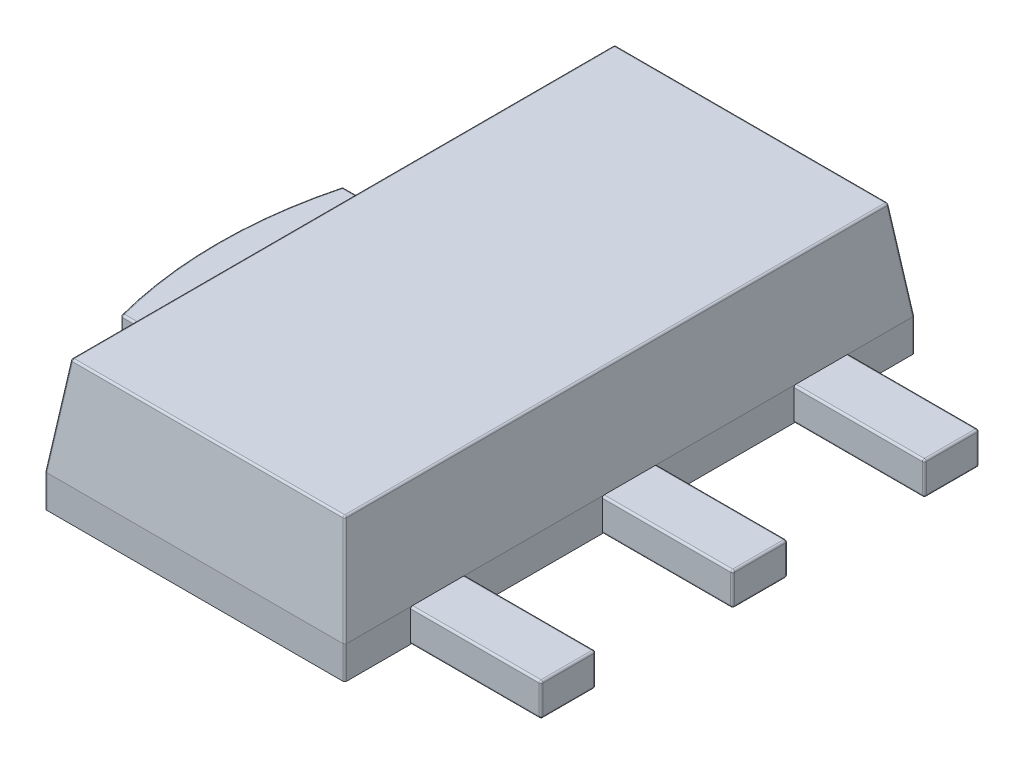
SolidWorks part; units mm, degrees
ref_plane "Front Plane" through (0, 0, 0) normal (0, 0, 1) x (1, 0, 0)
ref_plane "Top Plane" through (0, 0, 0) normal (0, 1, 0) x (1, 0, 0)
ref_plane "Right Plane" through (0, 0, 0) normal (1, 0, 0) x (0, 0, -1)
sketch "Sketch1" plane through (0, 0, 0) normal (0, 1, 0) x (1, 0, 0)
  line L1 (-1.15, -2.185) -> (1.15, -2.185)
  line L2 (-1.15, -2.185) -> (-1.15, 2.185)
  line L3 (-1.15, 2.185) -> (1.15, 2.185)
  line L4 (1.15, -2.185) -> (1.15, 2.185)
  line L5 (-1.15, -2.185) -> (1.15, 2.185) construction
  line L6 (-1.15, 2.185) -> (1.15, -2.185) construction
  point P0 (0, 0)
  dimension "D1" = 2.3
  dimension "D2" = 4.37
extrude "Boss-Extrude1" add sketch "Sketch1" along normal mid plane 1
sketch "Sketch2" plane through (0, 0, 2.185) normal (0, 0, 1) x (1, 0, 0)
  line L0 (-1.15, -0.25) -> (1.15, -0.25) construction
  line L1 (-1.15, 0.5) -> (-1.15, -0.5) construction
  line L2 (1.15, 0.5) -> (1.15, -0.5) construction
  line L3 (-1.15, -0.5) -> (1.15, -0.5) construction
  line L4 (-1.15, -0.25) -> (-1.15, 0.5)
  line L5 (-1.15, 0.5) -> (-1.05, 0.5)
  line L6 (-1.15, 0.5) -> (1.15, 0.5) construction
  line L7 (-1.05, 0.5) -> (-1.15, -0.25)
  line L8 (0, -0.25) -> (0, 0.5) construction
  line L9 (1.05, 0.5) -> (1.15, -0.25)
  line L10 (1.15, 0.5) -> (1.05, 0.5)
  line L11 (1.15, -0.25) -> (1.15, 0.5)
  dimension "D1" = 0.25
  dimension "D2" = 0.1
extrude "Cut-Extrude1" cut sketch "Sketch2" against normal through all
sketch "Sketch3" plane through (1.15, 0, 0) normal (1, 0, 0) x (0, 0, -1)
  line L0 (-2.185, -0.25) -> (-2.185, 0.5)
  line L1 (-2.185, 0.5) -> (-2.085, 0.5)
  line L2 (2.185, 0.5) -> (-2.185, 0.5) construction
  line L3 (-2.085, 0.5) -> (-2.185, -0.25)
  line L4 (0, 0) -> (0, 1.1486) construction
  line L5 (2.085, 0.5) -> (2.185, -0.25)
  line L6 (2.185, 0.5) -> (2.085, 0.5)
  line L7 (2.185, -0.25) -> (2.185, 0.5)
  dimension "D1" = 0.1
extrude "Cut-Extrude2" cut sketch "Sketch3" against normal through all
fillet "Fillet1" radius 0.015 12 edges at (0, 0.5, -2.085) (1.05, 0.5, 0) (0, 0.5, 2.085) (-1.05, 0.5, 0) (-1.15, -0.375, 2.185) (-1.1, 0.125, 2.135) (-1.15, -0.375, -2.185) (-1.1, 0.125, -2.135) (1.15, -0.375, -2.185) (1.1, 0.125, -2.135) (1.1, 0.125, 2.135) (1.15, -0.375, 2.185)
sketch "Sketch6" plane through (0, -0.5, 0) normal (0, -1, 0) x (1, 0, 0)
  line L0 (-1.15, -2.17) -> (-1.15, 2.17) construction
  line L5 (-1.15, 0.85) -> (-1.9, -0.85) construction
  line L6 (-1.15, -0.85) -> (-1.9, 0.85) construction
  line L7 (1.15, -2.17) -> (1.15, 2.17) construction
  line L12 (1.15, 0.21) -> (2.15, -0.21) construction
  line L13 (1.15, -0.21) -> (2.15, 0.21) construction
  line L14 (1.15, 1.68) -> (1.15, 1.26)
  line L15 (1.15, 1.68) -> (2.15, 1.68)
  line L16 (2.15, 1.68) -> (2.15, 1.26)
  line L17 (1.15, 1.26) -> (2.15, 1.26)
  line L18 (1.15, 0.21) -> (1.15, -0.21)
  line L19 (1.15, 0.21) -> (2.15, 0.21)
  line L20 (2.15, 0.21) -> (2.15, -0.21)
  line L21 (1.15, -0.21) -> (2.15, -0.21)
  line L22 (1.15, -1.26) -> (1.15, -1.68)
  line L23 (1.15, -1.26) -> (2.15, -1.26)
  line L24 (2.15, -1.26) -> (2.15, -1.68)
  line L25 (1.15, -1.68) -> (2.15, -1.68)
  line L26 (-1.9, 0.85) -> (-1.15, 0.85)
  line L27 (-1.15, 0.85) -> (-1.15, -0.85)
  line L28 (-1.9, -0.85) -> (-1.15, -0.85)
  arc A0 (-1.9, 0.85) -> (-1.9, -0.85) centre (1.2887, 0) ccw
  point P4 (-1.525, 0)
  point P13 (1.65, 0)
  dimension "D3" = 3.3
  dimension "D1" = 0.75
  dimension "D2" = 1.7
  dimension "D4" = 1
  dimension "D5" = 0.42
extrude "Boss-Extrude2" add sketch "Sketch6" against normal blind 0.25
fillet "Fillet2" radius 0.015 32 edges at (2.15, -0.375, 1.68) (2.15, -0.25, 1.47) (2.15, -0.375, 1.26) (2.15, -0.5, 1.47) (-1.525, -0.5, 0.85) (-1.525, -0.25, 0.85) (-1.9, -0.375, 0.85) (-2.0113, -0.5, 0) (-1.525, -0.5, -0.85) (-1.9, -0.375, -0.85) (-2.0113, -0.25, 0) (-1.525, -0.25, -0.85) (1.65, -0.5, -1.26) (2.15, -0.5, -1.47) (1.65, -0.5, -1.68) (2.15, -0.375, -1.68) (2.15, -0.375, -1.26) (1.65, -0.25, -1.26) (2.15, -0.25, -1.47) (1.65, -0.25, -1.68) (1.65, -0.5, -0.21) (2.15, -0.5, 0) (2.15, -0.375, -0.21) (2.15, -0.375, 0.21) (2.15, -0.25, 0) (1.65, -0.25, -0.21) (1.65, -0.5, 0.21) (1.65, -0.25, 0.21) (1.65, -0.5, 1.68) (1.65, -0.25, 1.26) (1.65, -0.5, 1.26) (1.65, -0.25, 1.68)
